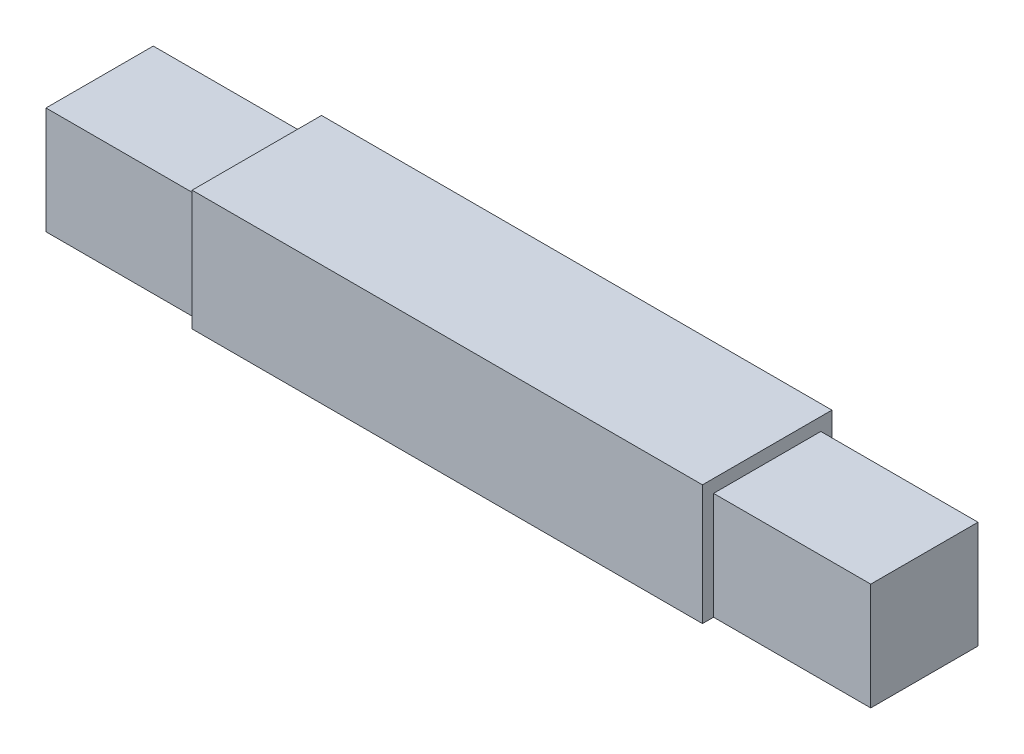
SolidWorks part; units mm, degrees
ref_plane "Front Plane" through (0, 0, 0) normal (0, 0, 1) x (1, 0, 0)
ref_plane "Top Plane" through (0, 0, 0) normal (0, 1, 0) x (1, 0, 0)
ref_plane "Right Plane" through (0, 0, 0) normal (1, 0, 0) x (0, 0, -1)
sketch "Sketch2" plane through (0, 0, 0) normal (0, 1, 0) x (1, 0, 0)
  line L1 (-28.321, -3.683) -> (28.321, -3.683)
  line L2 (-28.321, -3.683) -> (-28.321, 3.683)
  line L3 (-28.321, 3.683) -> (28.321, 3.683)
  line L4 (28.321, -3.683) -> (28.321, 3.683)
  line L5 (-28.321, -3.683) -> (28.321, 3.683) construction
  line L6 (-28.321, 3.683) -> (28.321, -3.683) construction
  line L7 (-17.526, -4.445) -> (17.526, -4.445)
  line L8 (-17.526, -4.445) -> (-17.526, 4.445)
  line L9 (-17.526, 4.445) -> (17.526, 4.445)
  line L10 (17.526, -4.445) -> (17.526, 4.445)
  line L11 (-17.526, -4.445) -> (17.526, 4.445) construction
  line L12 (-17.526, 4.445) -> (17.526, -4.445) construction
  point P0 (0, 0)
  point P6 (0, 0)
  dimension "D1" = 56.642
  dimension "D2" = 7.366
  dimension "D3" = 35.052
  dimension "D4" = 8.89
extrude "Boss-Extrude1" add sketch "Sketch2" along normal blind 7.366 contours L1 L8 L3 L2 | L10 L1 L4 L3 region at (-22.9235, 0, 0) region at (22.9235, 0, 0)
extrude "Boss-Extrude2" add sketch "Sketch2<4>" along normal blind 8.255 contours L3 L10 L9 L8 | L1 L10 L3 L8 | L7 L10 L1 L8 region at (0, 0, 0) region at (0, 0, 4.064) region at (0, 0, -4.064)
sketch "Sketch2<4>" plane through (0, 0, 0) normal (0, 1, 0) x (1, 0, 0) same geometry as "Sketch2"
